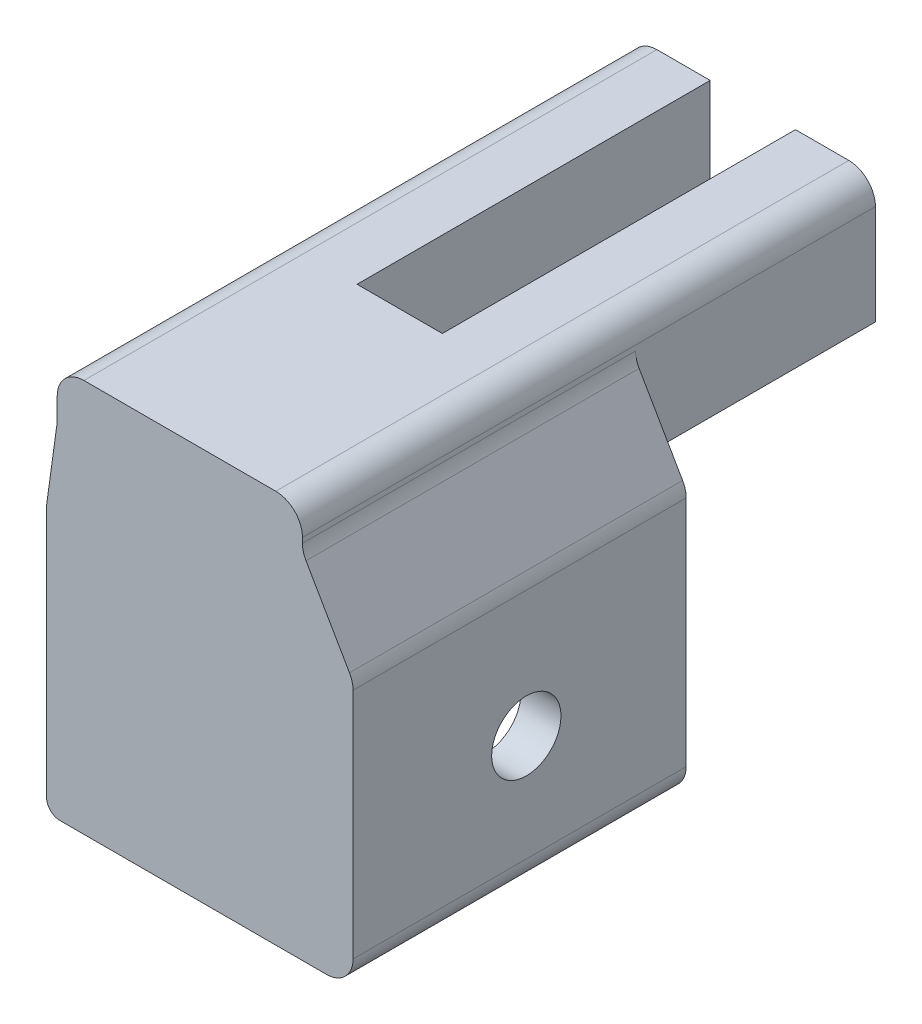
SolidWorks part; units mm, degrees
ref_plane "正面" through (0, 0, 0) normal (0, 0, 1) x (1, 0, 0)
ref_plane "平面" through (0, 0, 0) normal (0, 1, 0) x (1, 0, 0)
ref_plane "右側面" through (0, 0, 0) normal (1, 0, 0) x (0, 0, -1)
sketch "ｽｹｯﾁ1" plane through (0, 0, 0) normal (0, 0, 1) x (1, 0, 0)
  line L1 (-10, 10) -> (10, 10)
  line L2 (-10, 10) -> (-10, -10)
  line L3 (-10, -10) -> (10, -10)
  line L4 (10, 10) -> (10, -10)
  line L5 (-10, 10) -> (10, -10) construction
  line L6 (-10, -10) -> (10, 10) construction
  point P0 (0, 0)
  dimension "D1" = 20
extrude "ﾎﾞｽ - 押し出し1" add sketch "ｽｹｯﾁ1" along normal blind 3
sketch "ｽｹｯﾁ2" plane through (0, 0, 0) normal (0, 0, -1) x (-1, 0, 0)
  line L0 (-10, 10) -> (10, 10) construction
  line L1 (-3, 4) -> (3, 4)
  line L2 (-3, 4) -> (-3, 10)
  line L3 (-3, 10) -> (3, 10)
  line L4 (3, 4) -> (3, 10)
  line L5 (-3, 4) -> (3, 10) construction
  line L6 (-3, 10) -> (3, 4) construction
  line L7 (0, 0) -> (0, 7) construction
  point P0 (0, 7)
  dimension "D1" = 6
  dimension "D2" = 6
extrude "ﾎﾞｽ - 押し出し2" add sketch "ｽｹｯﾁ2" along normal blind 40
sketch "ｽｹｯﾁ3" plane through (0, 0, 3) normal (0, 0, 1) x (1, 0, 0)
  line L0 (-10, -10) -> (10, -10) construction
  line L1 (10, 10) -> (13, 10)
  line L2 (10, 10) -> (10, -10)
  line L3 (10, -10) -> (13, -10)
  line L4 (13, 10) -> (13, -10)
  dimension "D1" = 3
extrude "ﾎﾞｽ - 押し出し3" add sketch "ｽｹｯﾁ3" against normal blind 25
sketch "ｽｹｯﾁ4" plane through (13, 0, 0) normal (1, 0, 0) x (0, 0, -1)
  line L0 (0, 0) -> (22, 0) construction
  line L1 (22, -10) -> (22, 10) construction
  circle A0 centre (10, 0) radius 2.6
  dimension "D1" = 10
  dimension "D2" = 5.2
extrude "ｶｯﾄ - 押し出し1" cut sketch "ｽｹｯﾁ4" against normal up to next
fillet "ﾌｨﾚｯﾄ1" radius 1 1 edges at (-10, -10, 1.5)
ref_plane "平面1" through (0, 0, -13.5) normal (0, 0, -1) x (-1, 0, 0)
sketch "ｽｹｯﾁ5" plane through (0, 0, -13.5) normal (0, 0, -1) x (-1, 0, 0)
  line L0 (3, 10) -> (-3, 10) construction
  line L1 (-1.6, 6.1) -> (1.6, 6.1)
  line L2 (-1.6, 6.1) -> (-1.6, 10)
  line L3 (-1.6, 10) -> (1.6, 10)
  line L4 (1.6, 6.1) -> (1.6, 10)
  line L5 (-1.6, 6.1) -> (1.6, 10) construction
  line L6 (-1.6, 10) -> (1.6, 6.1) construction
  line L7 (0, 8.05) -> (0, 0) construction
  point P0 (0, 8.05)
  dimension "D1" = 3.2
  dimension "D2" = 3.9
extrude "ｶｯﾄ - 押し出し2" cut sketch "ｽｹｯﾁ5" along normal blind 30
sketch "ｽｹｯﾁ6" plane through (0, 0, 3) normal (0, 0, 1) x (1, 0, 0)
  line L0 (13, 10) -> (-10, 10) construction
  line L1 (3.2, 10) -> (9.2, 10)
  line L2 (3.2, 10) -> (3.2, 19.5)
  line L3 (3.2, 19.5) -> (9.2, 19.5)
  line L4 (9.2, 10) -> (9.2, 19.5)
  line L5 (0, 0) -> (0, 10) construction
  line L6 (-3.2, 19.5) -> (-9.2, 19.5)
  line L7 (-9.2, 10) -> (-9.2, 19.5)
  line L8 (-3.2, 10) -> (-9.2, 10)
  line L9 (-3.2, 10) -> (-3.2, 19.5)
  dimension "D1" = 6.4
  dimension "D2" = 9.5
  dimension "D3" = 6
extrude "ﾎﾞｽ - 押し出し4" add sketch "ｽｹｯﾁ6" against normal up to surface (43 mm away) up to face at (0, 7.525, -40)
sketch "ｽｹｯﾁ7" plane through (0, 0, 3) normal (0, 0, 1) x (1, 0, 0)
  line L1 (-3.2, 19.5) -> (3.2, 19.5)
  line L2 (-3.2, 19.5) -> (-3.2, 10)
  line L3 (-3.2, 10) -> (3.2, 10)
  line L4 (3.2, 19.5) -> (3.2, 10)
extrude "ﾎﾞｽ - 押し出し5" add sketch "ｽｹｯﾁ7" against normal blind 16.5
sketch "ｽｹｯﾁ8" plane through (0, 0, 3) normal (0, 0, 1) x (1, 0, 0)
  line L0 (13, 10) -> (9.2, 16.5818)
  line L1 (9.2, 10) -> (9.2, 19.5) construction
  line L2 (9.2, 16.5818) -> (9.2, 10)
  line L3 (9.2, 10) -> (13, 10)
  dimension "D1" = 60
extrude "ﾎﾞｽ - 押し出し6" add sketch "ｽｹｯﾁ8" against normal up to surface (25 mm away) up to face at (11.5, 0, -22)
fillet "ﾌｨﾚｯﾄ2" radius 2 5 edges at (13, -10, -9.5) (13, 10, -9.5) (9.2, 16.5818, -9.5) (9.2, 19.5, -18.5) (-9.2, 19.5, -18.5)
sketch "ｽｹｯﾁ9" plane through (0, 0, 3) normal (0, 0, 1) x (1, 0, 0)
  line L0 (-10, 10) -> (-9.2, 15.8)
  line L1 (-9.2, 17.5) -> (-9.2, 10) construction
  line L2 (-9.2, 15.8) -> (-9.2, 10)
  line L3 (-9.2, 10) -> (-10, 10)
  dimension "D1" = 5.8
extrude "ﾎﾞｽ - 押し出し7" add sketch "ｽｹｯﾁ9" against normal up to surface (43 mm away) up to face at (0, 7.525, -40)
sketch "ｽｹｯﾁ10" plane through (0, 0, -40) normal (0, 0, -1) x (-1, 0, 0)
  line L0 (3, 4) -> (3, 10) construction
  line L1 (1.6, 6.1) -> (3, 6.1)
  line L2 (1.6, 6.1) -> (1.6, 8.1)
  line L3 (1.6, 8.1) -> (3, 8.1)
  line L4 (3, 6.1) -> (3, 8.1)
  dimension "D1" = 2
extrude "ｶｯﾄ - 押し出し3" cut sketch "ｽｹｯﾁ10" against normal up to surface (26.5 mm away) up to face at (0, 11.12, -13.5)
fillet "ﾌｨﾚｯﾄ3" radius 0.5 2 edges at (-3, 8.1, -26.75) (-3, 6.1, -26.75)
fillet "ﾌｨﾚｯﾄ4" radius 1.5 2 edges at (3, 4, -20) (-3, 4, -20)
